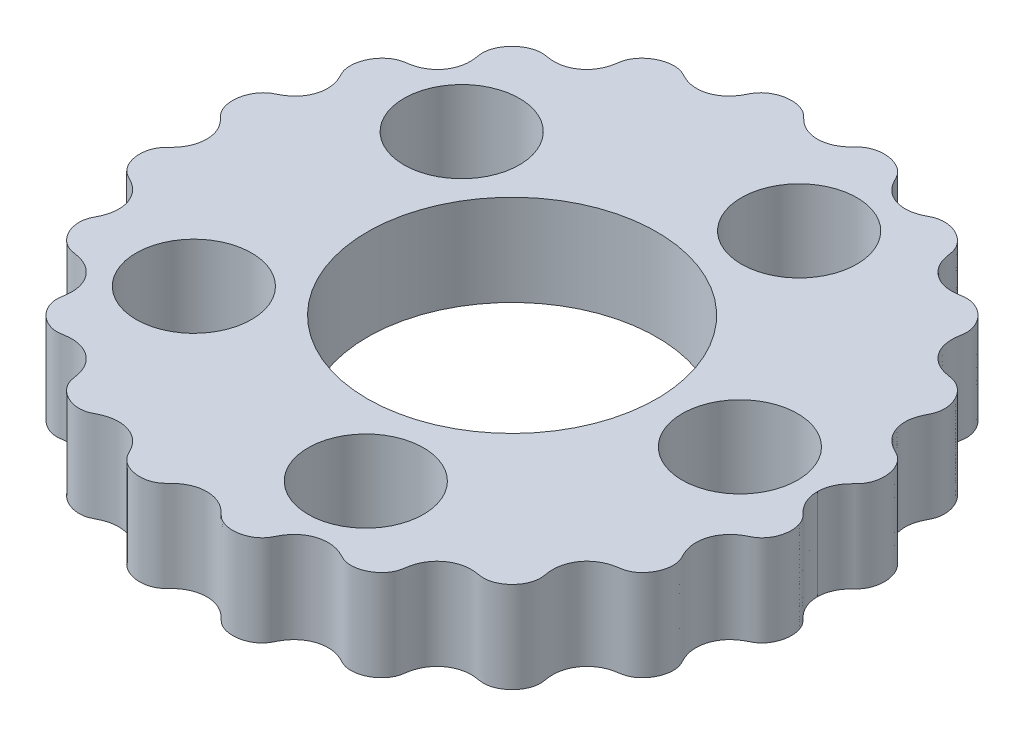
SolidWorks part; units mm, degrees
ref_plane "Front Plane" through (0, 0, 0) normal (0, 0, 1) x (1, 0, 0)
ref_plane "Top Plane" through (0, 0, 0) normal (0, 1, 0) x (1, 0, 0)
ref_plane "Right Plane" through (0, 0, 0) normal (1, 0, 0) x (0, 0, -1)
sketch "MAIN" plane through (0, 0, 0) normal (0, 1, 0) x (1, 0, 0)
  line L0 (-20.1, 0) -> (20.1, 0) construction
  line L1 (0, 0) -> (-0.8, 0)
  line L4 (0, -20.1) -> (0, 20.1) construction
  line L5 (-0.8, -20.2489) -> (-0.8, 20.2572) construction
  circle A22 centre (0, 0) radius 15
  circle A23 centre (15, 0) radius 3.8
  circle A24 centre (4.6353, -14.2658) radius 3.8
  circle A25 centre (-12.1353, -8.8168) radius 3.8
  circle A26 centre (-12.1353, 8.8168) radius 3.8
  circle A27 centre (4.6353, 14.2658) radius 3.8
  circle A29 centre (0, 0) radius 9.525
  spline S0 degree 4 poles (20.5886, 4.7068) (20.68, 4.6551) (20.8532, 4.5348) (21.1393, 4.2364) (21.3748, 3.7649) (21.4816, 3.2447) (21.4517, 2.7569) (21.3623, 2.4139) (21.2306, 2.1338) (21.0766, 1.9171) (20.8954, 1.7433) (20.7304, 1.5739) (20.553, 1.3627) (20.4068, 1.1453) (20.2874, 0.911) (20.1977, 0.6657) (20.1512, 0.4864) (20.1234, 0.3358) (20.1091, 0.21) (20.1026, 0.1123) (20.0996, 0.0252) (20.0999, -0.045) (20.1041, -0.1445) (20.1129, -0.2489) (20.1295, -0.3715) (20.1582, -0.5159) (20.2042, -0.6849) (20.2735, -0.8706) (20.3588, -1.0503) (20.459, -1.2218) (20.5666, -1.3754) (20.6778, -1.5121) (20.7891, -1.634) (20.8973, -1.7433) (21.0065, -1.8517) (21.1088, -1.9667) (21.2202, -2.1239) (21.3466, -2.3693) (21.4488, -2.7149) (21.4796, -3.1509) (21.4067, -3.6189) (21.2535, -4.0101) (21.0548, -4.3168) (20.8346, -4.5468) (20.6123, -4.7043) (20.3253, -4.8398) (20.0085, -5.0187) (19.6843, -5.2734) (19.3864, -5.6226) (19.1654, -6.0238) (19.0313, -6.4606) (18.9938, -6.8578) (19.019, -7.1969) (19.0763, -7.4737) (19.1428, -7.6897) (19.2312, -7.9077) (19.34, -8.1256) (19.4583, -8.3497) (19.5343, -8.602) (19.5712, -8.9102) (19.5475, -9.2683) (19.4413, -9.6634) (19.2307, -10.0711) (18.9626, -10.3939) (18.6946, -10.6074) (18.4633, -10.7327) (18.291, -10.7987) (18.1484, -10.8366) (18.0032, -10.862) (17.8576, -10.8843) (17.6411, -10.9233) (17.3574, -10.9968) (17.0179, -11.137) (16.6499, -11.3793) (16.3344, -11.6905) (16.085, -12.0601) (15.9134, -12.4744) (15.8373, -12.8617) (15.8261, -13.1985) (15.849, -13.4869) (15.8867, -13.7254) (15.9272, -13.9735) (15.9178, -14.2345) (15.8554, -14.5357) (15.7209, -14.8652) (15.4941, -15.2104) (15.1574, -15.5384) (14.7814, -15.7682) (14.4318, -15.8866) (14.1468, -15.9236) (13.9404, -15.918) (13.777, -15.8957) (13.5739, -15.8619) (13.3114, -15.8302) (12.9878, -15.8261) (12.6091, -15.8813) (12.2295, -16.0072) (11.877, -16.1993) (11.5634, -16.4525) (11.2997, -16.7592) (11.0942, -17.1092) (10.963, -17.4616) (10.8972, -17.764) (10.8626, -18.0051) (10.8228, -18.2154) (10.7561, -18.4196) (10.6183, -18.6831) (10.379, -18.9781) (10.0502, -19.2452) (9.6329, -19.4535) (9.2235, -19.5558) (8.8836, -19.5696) (8.6248, -19.5345) (8.4481, -19.4868) (8.3117, -19.4338) (8.1804, -19.3695) (8.0505, -19.3025) (7.8489, -19.2051) (7.5676, -19.0948) (7.1959, -19.0078) (6.7361, -18.9938) (6.2861, -19.0732) (5.8648, -19.241) (5.4886, -19.4879) (5.2101, -19.7619) (5.0117, -20.0304) (4.884, -20.2493) (4.8047, -20.4037) (4.7227, -20.5647) (4.6271, -20.7269) (4.4866, -20.8967) (4.2614, -21.0946) (3.9625, -21.275) (3.5833, -21.4148) (3.129, -21.4789) (2.7059, -21.4461) (2.3697, -21.3462) (2.1288, -21.223) (1.9722, -21.1131) (1.8575, -21.0121) (1.7229, -20.8767) (1.5347, -20.6912) (1.271, -20.4785) (0.9112, -20.275) (0.4846, -20.1344) (0.0431, -20.0821) (-0.3958, -20.1176) (-0.8148, -20.2365) (-1.152, -20.4058) (-1.4146, -20.5926) (-1.6227, -20.7757) (-1.7854, -20.9409) (-1.9581, -21.1102) (-2.1683, -21.2484) (-2.4378, -21.3695) (-2.7687, -21.4523) (-3.1582, -21.4754) (-3.5925, -21.4114) (-3.9625, -21.275) (-4.2614, -21.0946) (-4.4866, -20.8967) (-4.6271, -20.7269) (-4.7227, -20.5647) (-4.8047, -20.4037) (-4.884, -20.2493) (-5.0117, -20.0304) (-5.2101, -19.7619) (-5.4886, -19.4879) (-5.8648, -19.241) (-6.2861, -19.0732) (-6.7361, -18.9938) (-7.1959, -19.0078) (-7.5676, -19.0948) (-7.8489, -19.2051) (-8.0505, -19.3025) (-8.1804, -19.3695) (-8.3117, -19.4338) (-8.4481, -19.4868) (-8.6248, -19.5345) (-8.8836, -19.5696) (-9.2235, -19.5558) (-9.6329, -19.4535) (-10.0502, -19.2452) (-10.379, -18.9781) (-10.6183, -18.6831) (-10.7561, -18.4196) (-10.8228, -18.2154) (-10.8561, -18.0402) (-10.8777, -17.8992) (-10.9125, -17.6942) (-10.9754, -17.428) (-11.0942, -17.1093) (-11.2996, -16.7592) (-11.5634, -16.4525) (-11.877, -16.1993) (-12.2295, -16.0072) (-12.6091, -15.8813) (-12.9878, -15.8261) (-13.3114, -15.8302) (-13.5739, -15.8619) (-13.777, -15.8957) (-13.9404, -15.918) (-14.1468, -15.9236) (-14.4318, -15.8866) (-14.7814, -15.7682) (-15.1574, -15.5384) (-15.4941, -15.2104) (-15.7209, -14.8652) (-15.8554, -14.5357) (-15.9178, -14.2345) (-15.9272, -13.9735) (-15.8867, -13.7254) (-15.849, -13.4869) (-15.8261, -13.1985) (-15.8373, -12.8617) (-15.9134, -12.4744) (-16.085, -12.0601) (-16.3344, -11.6905) (-16.6499, -11.3793) (-17.0179, -11.137) (-17.3574, -10.9968) (-17.6411, -10.9233) (-17.8576, -10.8843) (-18.0032, -10.862) (-18.1484, -10.8366) (-18.291, -10.7987) (-18.4633, -10.7327) (-18.6946, -10.6074) (-18.9626, -10.3939) (-19.2307, -10.0711) (-19.4413, -9.6634) (-19.5475, -9.2683) (-19.5712, -8.9102) (-19.5343, -8.602) (-19.4583, -8.3497) (-19.34, -8.1256) (-19.2312, -7.9077) (-19.1215, -7.6374) (-19.0312, -7.3099) (-18.9886, -6.9144) (-19.0312, -6.4607) (-19.1654, -6.0238) (-19.3864, -5.6226) (-19.6843, -5.2734) (-20.0085, -5.0187) (-20.3253, -4.8398) (-20.6123, -4.7043) (-20.8346, -4.5468) (-21.0548, -4.3168) (-21.2535, -4.0101) (-21.4067, -3.6189) (-21.4796, -3.1509) (-21.4488, -2.7149) (-21.3466, -2.3693) (-21.2202, -2.1239) (-21.1088, -1.9667) (-21.0065, -1.8517) (-20.8973, -1.7433) (-20.7891, -1.634) (-20.6778, -1.5121) (-20.5666, -1.3754) (-20.459, -1.2218) (-20.3588, -1.0503) (-20.2735, -0.8706) (-20.2042, -0.6849) (-20.1582, -0.5159) (-20.1295, -0.3715) (-20.1129, -0.2489) (-20.1041, -0.1442) (-20.099, -0.0256) (-20.0999, 0.0597) (-20.107, 0.1917) (-20.1234, 0.3359) (-20.1512, 0.4864) (-20.1977, 0.6656) (-20.2874, 0.9112) (-20.4306, 1.1918) (-20.6222, 1.4599) (-20.8576, 1.7072) (-21.0766, 1.917) (-21.2306, 2.1338) (-21.3623, 2.4139) (-21.4517, 2.7569) (-21.4816, 3.2446) (-21.3748, 3.7649) (-21.1393, 4.2364) (-20.8532, 4.5348) (-20.68, 4.6551) (-20.5886, 4.7068) knots 0 0 0 0 0 0.004854 0.009708 0.018897 0.023991 0.029085 0.03214 0.035194 0.038248 0.041303 0.043723 0.046143 0.050984 0.053404 0.055825 0.058245 0.059455 0.060665 0.061539 0.062412 0.06356 0.064708 0.065855 0.067003 0.069298 0.071593 0.073888 0.076184 0.078479 0.080774 0.082553 0.084332 0.086111 0.08789 0.089668 0.091447 0.095005 0.100606 0.106208 0.111478 0.116748 0.119878 0.123007 0.126137 0.129267 0.13454 0.139813 0.145086 0.150359 0.155581 0.160804 0.163415 0.166026 0.168637 0.171249 0.174275 0.177302 0.180329 0.183356 0.188577 0.193798 0.19911 0.204423 0.207831 0.209535 0.211238 0.212942 0.214646 0.21635 0.218053 0.223116 0.228179 0.233242 0.238305 0.243486 0.248667 0.253849 0.25644 0.25903 0.262031 0.265031 0.268031 0.271032 0.27621 0.281388 0.286995 0.292602 0.296412 0.298318 0.300223 0.302128 0.304034 0.307844 0.312446 0.317047 0.321648 0.32625 0.330919 0.335589 0.340258 0.344928 0.348227 0.349876 0.351526 0.354825 0.358123 0.363551 0.368978 0.374256 0.379533 0.382914 0.384604 0.386294 0.387984 0.389675 0.391365 0.393055 0.39834 0.403624 0.408909 0.414194 0.419326 0.424458 0.429589 0.432155 0.434721 0.43617 0.437618 0.440515 0.443412 0.44631 0.451439 0.456568 0.46197 0.467372 0.470904 0.47267 0.474436 0.476202 0.477968 0.4815 0.486659 0.491818 0.496977 0.502136 0.507093 0.51205 0.517007 0.519485 0.521964 0.524855 0.527745 0.530636 0.533527 0.538479 0.543432 0.548561 0.55369 0.556588 0.559485 0.562382 0.56383 0.565279 0.567845 0.570411 0.575542 0.580674 0.585806 0.591091 0.596376 0.60166 0.606945 0.608635 0.610325 0.612016 0.613706 0.615396 0.617086 0.620467 0.625744 0.631022 0.636449 0.641877 0.645175 0.648474 0.650124 0.651773 0.653423 0.655072 0.659742 0.664411 0.669081 0.67375 0.678352 0.682953 0.687554 0.692156 0.695966 0.697872 0.699777 0.701682 0.703588 0.707398 0.713005 0.718612 0.72379 0.728968 0.731969 0.734969 0.737969 0.74097 0.74356 0.746151 0.751333 0.756514 0.761695 0.766758 0.771821 0.776884 0.781947 0.78365 0.785354 0.787058 0.788762 0.790465 0.792169 0.795577 0.80089 0.806202 0.811423 0.816644 0.819671 0.822698 0.825725 0.828751 0.831363 0.833974 0.839196 0.844419 0.849641 0.854914 0.860187 0.86546 0.870733 0.873863 0.876993 0.880122 0.883252 0.888522 0.893792 0.899394 0.904995 0.908553 0.910332 0.91211 0.913889 0.915668 0.917447 0.919226 0.921521 0.923816 0.926112 0.928407 0.930702 0.932997 0.934145 0.935292 0.93644 0.937588 0.939335 0.940545 0.941755 0.944175 0.946596 0.949016 0.953857 0.958697 0.961752 0.964806 0.96786 0.970915 0.976009 0.981103 0.990292 0.995146 1 1 1 1 1 construction
  spline S1 degree 4 poles (20.1, 0) (20.1, -0.0217) (20.1007, -0.0652) (20.1041, -0.1445) (20.1129, -0.2489) (20.1295, -0.3715) (20.1582, -0.5159) (20.2042, -0.6849) (20.2735, -0.8706) (20.3588, -1.0503) (20.459, -1.2218) (20.5666, -1.3754) (20.6778, -1.5121) (20.7891, -1.634) (20.8973, -1.7433) (21.0065, -1.8517) (21.1088, -1.9667) (21.2202, -2.1239) (21.3466, -2.3693) (21.4488, -2.7149) (21.4796, -3.1509) (21.4067, -3.6189) (21.2535, -4.0101) (21.0548, -4.3168) (20.8346, -4.5468) (20.6123, -4.7043) (20.3253, -4.8398) (20.0085, -5.0187) (19.6843, -5.2734) (19.3864, -5.6226) (19.1654, -6.0238) (19.0313, -6.4606) (18.9938, -6.8578) (19.019, -7.1969) (19.0763, -7.4737) (19.1428, -7.6897) (19.2312, -7.9077) (19.34, -8.1256) (19.4583, -8.3497) (19.5343, -8.602) (19.5712, -8.9102) (19.5475, -9.2683) (19.4413, -9.6634) (19.2307, -10.0711) (18.9626, -10.3939) (18.6946, -10.6074) (18.4633, -10.7327) (18.291, -10.7987) (18.1484, -10.8366) (18.0032, -10.862) (17.8576, -10.8843) (17.6411, -10.9233) (17.3574, -10.9968) (17.0179, -11.137) (16.6499, -11.3793) (16.3344, -11.6905) (16.085, -12.0601) (15.9134, -12.4744) (15.8373, -12.8617) (15.8261, -13.1985) (15.849, -13.4869) (15.8867, -13.7254) (15.9272, -13.9735) (15.9178, -14.2345) (15.8554, -14.5357) (15.7209, -14.8652) (15.4941, -15.2104) (15.1574, -15.5384) (14.7814, -15.7682) (14.4318, -15.8866) (14.1468, -15.9236) (13.9404, -15.918) (13.777, -15.8957) (13.5739, -15.8619) (13.3114, -15.8302) (12.9878, -15.8261) (12.6091, -15.8813) (12.2295, -16.0072) (11.877, -16.1993) (11.5634, -16.4525) (11.2997, -16.7592) (11.0942, -17.1092) (10.963, -17.4616) (10.8972, -17.764) (10.8626, -18.0051) (10.8228, -18.2154) (10.7561, -18.4196) (10.6183, -18.6831) (10.379, -18.9781) (10.0502, -19.2452) (9.6329, -19.4535) (9.2235, -19.5558) (8.8836, -19.5696) (8.6248, -19.5345) (8.4481, -19.4868) (8.3117, -19.4338) (8.1804, -19.3695) (8.0505, -19.3025) (7.8489, -19.2051) (7.5676, -19.0948) (7.1959, -19.0078) (6.7361, -18.9938) (6.2861, -19.0732) (5.8648, -19.241) (5.4886, -19.4879) (5.2101, -19.7619) (5.0117, -20.0304) (4.884, -20.2493) (4.8047, -20.4037) (4.7227, -20.5647) (4.6271, -20.7269) (4.4866, -20.8967) (4.2614, -21.0946) (3.9625, -21.275) (3.5833, -21.4148) (3.129, -21.4789) (2.7059, -21.4461) (2.3697, -21.3462) (2.1288, -21.223) (1.9722, -21.1131) (1.8575, -21.0121) (1.7229, -20.8767) (1.5347, -20.6912) (1.271, -20.4785) (0.9112, -20.275) (0.4846, -20.1344) (0.0431, -20.0821) (-0.3958, -20.1176) (-0.8148, -20.2365) (-1.152, -20.4058) (-1.4146, -20.5926) (-1.6227, -20.7757) (-1.7854, -20.9409) (-1.9581, -21.1102) (-2.1683, -21.2484) (-2.4378, -21.3695) (-2.7687, -21.4523) (-3.1582, -21.4754) (-3.5925, -21.4114) (-3.9625, -21.275) (-4.2614, -21.0946) (-4.4866, -20.8967) (-4.6271, -20.7269) (-4.7227, -20.5647) (-4.8047, -20.4037) (-4.884, -20.2493) (-5.0117, -20.0304) (-5.2101, -19.7619) (-5.4886, -19.4879) (-5.8648, -19.241) (-6.2861, -19.0732) (-6.7361, -18.9938) (-7.1959, -19.0078) (-7.5676, -19.0948) (-7.8489, -19.2051) (-8.0505, -19.3025) (-8.1804, -19.3695) (-8.3117, -19.4338) (-8.4481, -19.4868) (-8.6248, -19.5345) (-8.8836, -19.5696) (-9.2235, -19.5558) (-9.6329, -19.4535) (-10.0502, -19.2452) (-10.379, -18.9781) (-10.6183, -18.6831) (-10.7561, -18.4196) (-10.8228, -18.2154) (-10.8561, -18.0402) (-10.8777, -17.8992) (-10.9125, -17.6942) (-10.9754, -17.428) (-11.0942, -17.1093) (-11.2996, -16.7592) (-11.5634, -16.4525) (-11.877, -16.1993) (-12.2295, -16.0072) (-12.6091, -15.8813) (-12.9878, -15.8261) (-13.3114, -15.8302) (-13.5739, -15.8619) (-13.777, -15.8957) (-13.9404, -15.918) (-14.1468, -15.9236) (-14.4318, -15.8866) (-14.7814, -15.7682) (-15.1574, -15.5384) (-15.4941, -15.2104) (-15.7209, -14.8652) (-15.8554, -14.5357) (-15.9178, -14.2345) (-15.9272, -13.9735) (-15.8867, -13.7254) (-15.849, -13.4869) (-15.8261, -13.1985) (-15.8373, -12.8617) (-15.9134, -12.4744) (-16.085, -12.0601) (-16.3344, -11.6905) (-16.6499, -11.3793) (-17.0179, -11.137) (-17.3574, -10.9968) (-17.6411, -10.9233) (-17.8576, -10.8843) (-18.0032, -10.862) (-18.1484, -10.8366) (-18.291, -10.7987) (-18.4633, -10.7327) (-18.6946, -10.6074) (-18.9626, -10.3939) (-19.2307, -10.0711) (-19.4413, -9.6634) (-19.5475, -9.2683) (-19.5712, -8.9102) (-19.5343, -8.602) (-19.4583, -8.3497) (-19.34, -8.1256) (-19.2312, -7.9077) (-19.1215, -7.6374) (-19.0312, -7.3099) (-18.9886, -6.9144) (-19.0312, -6.4607) (-19.1654, -6.0238) (-19.3864, -5.6226) (-19.6843, -5.2734) (-20.0085, -5.0187) (-20.3253, -4.8398) (-20.6123, -4.7043) (-20.8346, -4.5468) (-21.0548, -4.3168) (-21.2535, -4.0101) (-21.4067, -3.6189) (-21.4796, -3.1509) (-21.4488, -2.7149) (-21.3466, -2.3693) (-21.2202, -2.1239) (-21.1088, -1.9667) (-21.0065, -1.8517) (-20.8973, -1.7433) (-20.7891, -1.634) (-20.6778, -1.5121) (-20.5666, -1.3754) (-20.459, -1.2218) (-20.3588, -1.0503) (-20.2735, -0.8706) (-20.2042, -0.6849) (-20.1582, -0.5159) (-20.1295, -0.3715) (-20.1129, -0.2489) (-20.1041, -0.1442) (-20.1007, -0.0655) (-20.1, -0.0217) (-20.1, 0) knots 0.062412 0.062412 0.062412 0.062412 0.062412 0.06356 0.064708 0.065855 0.067003 0.069298 0.071593 0.073888 0.076184 0.078479 0.080774 0.082553 0.084332 0.086111 0.08789 0.089668 0.091447 0.095005 0.100606 0.106208 0.111478 0.116748 0.119878 0.123007 0.126137 0.129267 0.13454 0.139813 0.145086 0.150359 0.155581 0.160804 0.163415 0.166026 0.168637 0.171249 0.174275 0.177302 0.180329 0.183356 0.188577 0.193798 0.19911 0.204423 0.207831 0.209535 0.211238 0.212942 0.214646 0.21635 0.218053 0.223116 0.228179 0.233242 0.238305 0.243486 0.248667 0.253849 0.25644 0.25903 0.262031 0.265031 0.268031 0.271032 0.27621 0.281388 0.286995 0.292602 0.296412 0.298318 0.300223 0.302128 0.304034 0.307844 0.312446 0.317047 0.321648 0.32625 0.330919 0.335589 0.340258 0.344928 0.348227 0.349876 0.351526 0.354825 0.358123 0.363551 0.368978 0.374256 0.379533 0.382914 0.384604 0.386294 0.387984 0.389675 0.391365 0.393055 0.39834 0.403624 0.408909 0.414194 0.419326 0.424458 0.429589 0.432155 0.434721 0.43617 0.437618 0.440515 0.443412 0.44631 0.451439 0.456568 0.46197 0.467372 0.470904 0.47267 0.474436 0.476202 0.477968 0.4815 0.486659 0.491818 0.496977 0.502136 0.507093 0.51205 0.517007 0.519485 0.521964 0.524855 0.527745 0.530636 0.533527 0.538479 0.543432 0.548561 0.55369 0.556588 0.559485 0.562382 0.56383 0.565279 0.567845 0.570411 0.575542 0.580674 0.585806 0.591091 0.596376 0.60166 0.606945 0.608635 0.610325 0.612016 0.613706 0.615396 0.617086 0.620467 0.625744 0.631022 0.636449 0.641877 0.645175 0.648474 0.650124 0.651773 0.653423 0.655072 0.659742 0.664411 0.669081 0.67375 0.678352 0.682953 0.687554 0.692156 0.695966 0.697872 0.699777 0.701682 0.703588 0.707398 0.713005 0.718612 0.72379 0.728968 0.731969 0.734969 0.737969 0.74097 0.74356 0.746151 0.751333 0.756514 0.761695 0.766758 0.771821 0.776884 0.781947 0.78365 0.785354 0.787058 0.788762 0.790465 0.792169 0.795577 0.80089 0.806202 0.811423 0.816644 0.819671 0.822698 0.825725 0.828751 0.831363 0.833974 0.839196 0.844419 0.849641 0.854914 0.860187 0.86546 0.870733 0.873863 0.876993 0.880122 0.883252 0.888522 0.893792 0.899394 0.904995 0.908553 0.910332 0.91211 0.913889 0.915668 0.917447 0.919226 0.921521 0.923816 0.926112 0.928407 0.930702 0.932997 0.934145 0.935292 0.93644 0.937588 0.937588 0.937588 0.937588 0.937588
  spline S2 degree 4 poles (20.1, 0) (20.1, 0.016) (20.1004, 0.0483) (20.103, 0.1222) (20.112, 0.2418) (20.1299, 0.3658) (20.1605, 0.5103) (20.2009, 0.6519) (20.2511, 0.7903) (20.3105, 0.925) (20.405, 1.1055) (20.5226, 1.2843) (20.6637, 1.4579) (20.8251, 1.6262) (20.9585, 1.7565) (21.084, 1.8949) (21.1907, 2.0485) (21.3222, 2.2956) (21.4364, 2.6526) (21.4803, 3.1177) (21.4039, 3.6005) (21.2554, 3.9885) (21.0881, 4.2662) (20.9406, 4.4515) (20.7839, 4.6031) (20.6242, 4.7228) (20.4498, 4.8192) (20.2714, 4.9072) (20.0538, 5.0278) (19.7727, 5.2201) (19.4603, 5.5221) (19.1704, 5.9791) (19.0001, 6.551) (18.9968, 7.0935) (19.1004, 7.5221) (19.226, 7.825) (19.3231, 8.0197) (19.4032, 8.1742) (19.4892, 8.3744) (19.5665, 8.6825) (19.5779, 9.1011) (19.4647, 9.6109) (19.2312, 10.0617) (18.9516, 10.3963) (18.6873, 10.6122) (18.4786, 10.7388) (18.2767, 10.8266) (18.088, 10.8805) (17.8946, 10.9117) (17.7013, 10.9419) (17.5098, 10.9831) (17.3219, 11.0382) (17.0549, 11.141) (16.7249, 11.3247) (16.3639, 11.6361) (16.0441, 12.1125) (15.8775, 12.6141) (15.841, 13.046) (15.8658, 13.3784) (15.9011, 13.611) (15.9319, 13.7968) (15.9482, 14.0321) (15.9148, 14.3537) (15.7871, 14.7447) (15.5207, 15.1776) (15.173, 15.5163) (14.8159, 15.7409) (14.503, 15.8642) (14.2676, 15.9213) (14.0488, 15.9441) (13.8511, 15.9387) (13.6559, 15.909) (13.4613, 15.8774) (13.265, 15.8568) (13.0677, 15.8506) (12.7762, 15.8657) (12.3956, 15.941) (11.9386, 16.1371) (11.4706, 16.5199) (11.1629, 16.9705) (11.0089, 17.3828) (10.9417, 17.7007) (10.9094, 17.9106) (10.8813, 18.0783) (10.8259, 18.2838) (10.7008, 18.5665) (10.4632, 18.8965) (10.1065, 19.2033) (9.6723, 19.4296) (9.2327, 19.5511) (8.8627, 19.5763) (8.5739, 19.5408) (8.3713, 19.483) (8.2335, 19.4293) (8.1088, 19.3698) (7.9719, 19.2984) (7.8178, 19.2242) (7.6203, 19.1423) (7.3752, 19.0655) (7.0593, 19.0086) (6.6743, 19.0056) (6.2349, 19.0853) (5.7672, 19.2865) (5.3804, 19.5853) (5.1146, 19.9125) (4.9536, 20.1837) (4.8383, 20.4088) (4.7236, 20.6354) (4.5008, 20.9158) (4.1338, 21.1948) (3.6506, 21.4015) (3.1414, 21.4742) (2.7011, 21.4391) (2.3677, 21.3457) (2.1404, 21.2452) (1.9708, 21.1395) (1.8527, 21.0456) (1.7606, 20.9601) (1.6892, 20.8895) (1.6182, 20.8184) (1.546, 20.7486) (1.4535, 20.6637) (1.3379, 20.5669) (1.1957, 20.4632) (0.9444, 20.3112) (0.5869, 20.1608) (0.0974, 20.0677) (-0.5067, 20.1237) (-1.0106, 20.3249) (-1.3647, 20.5768) (-1.5935, 20.7925) (-1.7318, 20.9329) (-1.8462, 21.0415) (-2.0019, 21.1628) (-2.2547, 21.308) (-2.6214, 21.4316) (-3.112, 21.4794) (-3.6642, 21.3957) (-4.1338, 21.1948) (-4.5008, 20.9158) (-4.7236, 20.6354) (-4.8383, 20.4088) (-4.9536, 20.1837) (-5.1146, 19.9125) (-5.3804, 19.5853) (-5.7672, 19.2865) (-6.2349, 19.0853) (-6.6743, 19.0056) (-7.0593, 19.0086) (-7.3752, 19.0655) (-7.6203, 19.1423) (-7.8178, 19.2242) (-7.9719, 19.2984) (-8.1088, 19.3698) (-8.2335, 19.4293) (-8.3713, 19.483) (-8.5739, 19.5408) (-8.8627, 19.5763) (-9.2327, 19.5511) (-9.6723, 19.4296) (-10.1065, 19.2033) (-10.4632, 18.8965) (-10.7008, 18.5665) (-10.8259, 18.2838) (-10.8813, 18.0783) (-10.9094, 17.9106) (-10.9417, 17.7007) (-11.0089, 17.3828) (-11.1629, 16.9705) (-11.4705, 16.5199) (-11.9386, 16.1371) (-12.4415, 15.9213) (-12.8743, 15.8493) (-13.2159, 15.8516) (-13.4613, 15.8774) (-13.6559, 15.909) (-13.8511, 15.9387) (-14.0488, 15.9441) (-14.2676, 15.9213) (-14.503, 15.8642) (-14.8159, 15.7409) (-15.173, 15.5163) (-15.5207, 15.1776) (-15.7871, 14.7447) (-15.9148, 14.3537) (-15.9482, 14.0321) (-15.9319, 13.7968) (-15.9011, 13.611) (-15.8658, 13.3784) (-15.841, 13.046) (-15.8775, 12.6141) (-16.0441, 12.1125) (-16.3639, 11.6361) (-16.7249, 11.3247) (-17.0549, 11.141) (-17.3219, 11.0382) (-17.5098, 10.9831) (-17.7013, 10.9419) (-17.8946, 10.9117) (-18.088, 10.8805) (-18.2767, 10.8266) (-18.4786, 10.7388) (-18.6873, 10.6122) (-18.9516, 10.3963) (-19.2312, 10.0617) (-19.4647, 9.6109) (-19.5779, 9.1011) (-19.5665, 8.6825) (-19.4892, 8.3744) (-19.4032, 8.1742) (-19.3231, 8.0197) (-19.226, 7.825) (-19.1004, 7.5221) (-18.9968, 7.0935) (-19.0001, 6.551) (-19.1704, 5.9791) (-19.4603, 5.5221) (-19.7727, 5.2201) (-20.0538, 5.0278) (-20.2714, 4.9072) (-20.4498, 4.8192) (-20.6242, 4.7228) (-20.7839, 4.6031) (-20.9406, 4.4515) (-21.0881, 4.2662) (-21.2554, 3.9885) (-21.4039, 3.6005) (-21.4803, 3.1177) (-21.4364, 2.6526) (-21.3222, 2.2956) (-21.1907, 2.0485) (-21.084, 1.8949) (-20.9585, 1.7565) (-20.8251, 1.6262) (-20.6637, 1.4579) (-20.5226, 1.2843) (-20.405, 1.1055) (-20.3105, 0.925) (-20.2511, 0.7903) (-20.2009, 0.6519) (-20.1605, 0.5103) (-20.1299, 0.3658) (-20.112, 0.2419) (-20.103, 0.1218) (-20.1004, 0.0485) (-20.1, 0.016) (-20.1, 0) knots 0.063609 0.063609 0.063609 0.063609 0.063609 0.064458 0.065307 0.067005 0.068703 0.070402 0.0721 0.073798 0.075496 0.077194 0.0815 0.083653 0.085806 0.087958 0.090111 0.092264 0.094417 0.100851 0.107286 0.113599 0.116755 0.119912 0.122208 0.124504 0.1268 0.129096 0.131392 0.133688 0.13828 0.144787 0.151294 0.158382 0.16547 0.169487 0.171496 0.173504 0.175513 0.177521 0.181538 0.188089 0.19464 0.201359 0.204718 0.208078 0.210337 0.212596 0.214854 0.217113 0.219372 0.221631 0.22389 0.226149 0.232563 0.238978 0.24565 0.252321 0.256667 0.25884 0.261013 0.263186 0.265358 0.269704 0.275849 0.281993 0.288591 0.29189 0.295189 0.297466 0.299742 0.302018 0.304295 0.306571 0.308848 0.311124 0.3134 0.320031 0.326662 0.333804 0.340946 0.344869 0.34683 0.348792 0.350753 0.352715 0.356638 0.362993 0.369347 0.374207 0.379066 0.383919 0.386345 0.387558 0.388771 0.390744 0.392717 0.39469 0.396663 0.400609 0.404555 0.40945 0.414345 0.42109 0.427836 0.431732 0.433681 0.435629 0.439525 0.443422 0.450062 0.456701 0.463502 0.466903 0.470303 0.472622 0.474941 0.476101 0.47726 0.47842 0.479579 0.480739 0.481898 0.484217 0.486536 0.488855 0.49544 0.502026 0.50926 0.516494 0.520133 0.521952 0.523772 0.525591 0.527411 0.53105 0.537174 0.543299 0.549938 0.556578 0.560475 0.564371 0.566319 0.568268 0.572164 0.57891 0.585655 0.59055 0.595445 0.599391 0.603337 0.60531 0.607283 0.609256 0.611229 0.612442 0.613655 0.616081 0.620934 0.625793 0.630653 0.637007 0.643362 0.647285 0.649247 0.651208 0.65317 0.655131 0.659054 0.666196 0.673338 0.679969 0.6866 0.691152 0.693429 0.695705 0.697982 0.700258 0.702534 0.704811 0.70811 0.711409 0.718007 0.724151 0.730296 0.734642 0.736814 0.738987 0.74116 0.743333 0.747679 0.75435 0.761022 0.767437 0.773851 0.77611 0.778369 0.780628 0.782887 0.785146 0.787404 0.789663 0.791922 0.795282 0.798641 0.80536 0.811911 0.818462 0.822479 0.824487 0.826496 0.828504 0.830513 0.83453 0.841618 0.848706 0.855213 0.86172 0.866312 0.868608 0.870904 0.8732 0.875496 0.877792 0.880088 0.883245 0.886401 0.892714 0.899149 0.905583 0.907736 0.909889 0.912042 0.914194 0.916347 0.9185 0.922806 0.924504 0.926202 0.9279 0.929598 0.931297 0.932995 0.934693 0.935542 0.936391 0.936391 0.936391 0.936391 0.936391
  point P67 (0, 0)
  dimension "D1" = 19.05
  dimension "D4" = 30
  dimension "D5" = 7.6
  dimension "D6" = 5
extrude "Boss-Extrude1" add sketch "MAIN" along normal blind 6 from offset 1 contours S1 S2 A27 A22 A23 A24 A25 A26 | A27 A22 A26 A25 A24 A23 A29 region at (10.7791, 0, 0) region at (0, 0, 19.4931)
